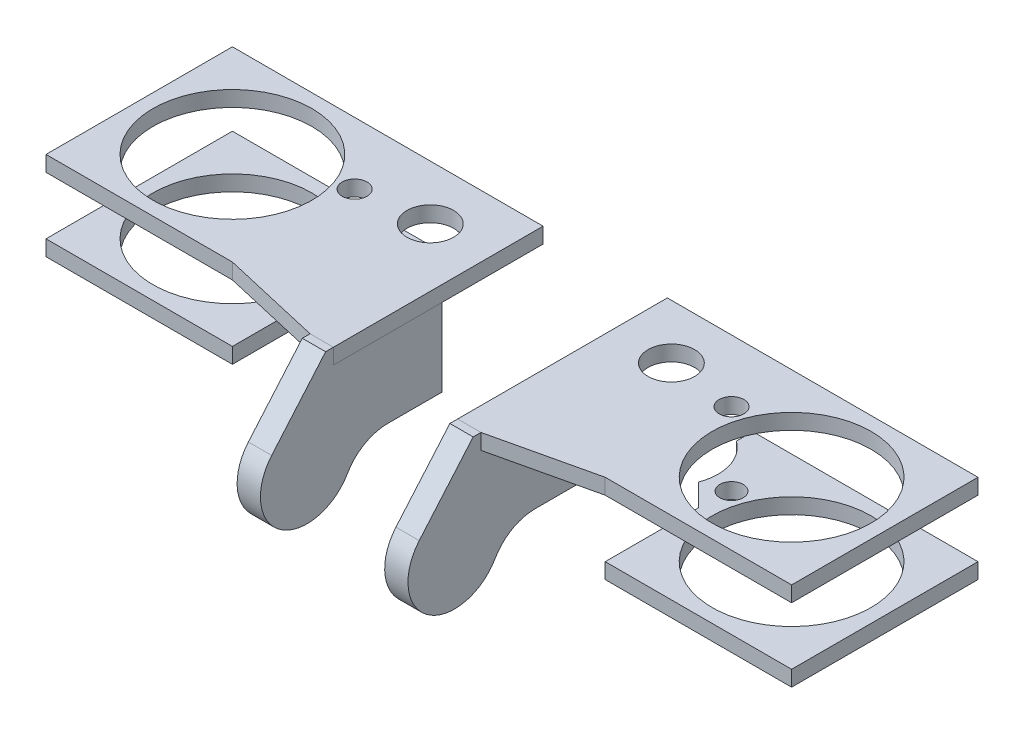
SolidWorks part; units mm, degrees
material "Alum Plate"
ref_plane "Front Plane" through (0, 0, 0) normal (0, 0, 1) x (1, 0, 0)
ref_plane "Top Plane" through (0, 0, 0) normal (0, 1, 0) x (1, 0, 0)
ref_plane "Right Plane" through (0, 0, 0) normal (1, 0, 0) x (0, 0, -1)
sketch "Sketch1" plane through (0, 0, 0) normal (0, 1, 0) x (1, 0, 0)
  line L0 (0, 0) -> (114.3, 0) construction
  line L1 (-114.3, 0) -> (0, 0) construction
  line L3 (-9.525, 158.75) -> (-3.175, 158.75)
  line L4 (-9.525, 158.75) -> (-9.525, 44.45)
  line L5 (-9.525, 44.45) -> (-3.175, 44.45)
  line L6 (-3.175, 158.75) -> (-3.175, 44.45)
  line L7 (-9.525, 158.75) -> (-3.175, 44.45) construction
  line L8 (-9.525, 44.45) -> (-3.175, 158.75) construction
  line L14 (-152.4, -76.2) -> (152.4, -76.2)
  line L18 (-114.3, 0) -> (-49.2756, 15.875) construction
  line L19 (49.2756, 15.875) -> (114.3, 0) construction
  line L20 (-25.4, 38.1) -> (0, 38.1) construction
  line L21 (-6.35, 101.6) -> (0, 101.6)
  line L29 (0, 0) -> (0, -25.4) construction
  line L30 (-114.3, 0) -> (-77.0346, 12.7) construction
  line L43 (-77.0346, 12.7) -> (-49.2756, 15.875) construction
  line L44 (49.2756, 15.875) -> (77.0346, 12.7) construction
  line L55 (77.0346, 12.7) -> (114.3, 0) construction
  line L69 (-152.4, -76.2) -> (-152.4, 38.1)
  line L70 (-152.4, 38.1) -> (152.4, 38.1)
  line L71 (152.4, -76.2) -> (152.4, 38.1)
  line L78 (0, 101.6) -> (0, -25.4)
  line L79 (0, -25.4) -> (0, -152.4) construction
  line L80 (-9.525, -209.55) -> (-3.175, -209.55) construction
  line L81 (-9.525, -209.55) -> (-9.525, -95.25) construction
  line L82 (-9.525, -95.25) -> (-3.175, -95.25) construction
  line L83 (-3.175, -209.55) -> (-3.175, -95.25) construction
  line L84 (-9.525, -209.55) -> (-3.175, -95.25) construction
  line L85 (-9.525, -95.25) -> (-3.175, -209.55) construction
  line L86 (0, -152.4) -> (-6.35, -152.4) construction
  line L87 (-34.925, -76.2) -> (-25.4, -76.2)
  line L88 (-34.925, -76.2) -> (-34.925, 38.1)
  line L89 (-34.925, 38.1) -> (-25.4, 38.1)
  line L90 (-25.4, -76.2) -> (-25.4, 38.1)
  line L91 (34.925, -76.2) -> (25.4, -76.2)
  line L92 (34.925, -76.2) -> (34.925, 38.1)
  line L93 (34.925, 38.1) -> (25.4, 38.1)
  line L94 (25.4, -76.2) -> (25.4, 38.1)
  line L95 (0, 38.1) -> (25.4, 38.1) construction
  circle A0 centre (-114.3, 0) radius 32.5
  circle A1 centre (-114.3, 0) radius 25
  circle A2 centre (114.3, 0) radius 32.5
  circle A3 centre (114.3, 0) radius 25
  circle A4 centre (-49.2756, 15.875) radius 17.5006
  circle A5 centre (49.2756, 15.875) radius 17.5006
  circle A6 centre (-77.0346, 12.7) radius 22.86
  circle A7 centre (77.0346, 12.7) radius 22.86
  point P8 (-6.35, 101.6)
  point P21 (114.3, 32.5)
  point P25 (49.2756, 33.3756)
  point P29 (49.2756, -1.6256)
  point P31 (0, -76.2)
  point P32 (-6.35, -152.4)
  point P62 (146.8, 0)
  dimension "D1" = 50
  dimension "D2" = 65
  dimension "D8" = 35.0012
  dimension "D11" = 127
  dimension "D12" = 63.5
  dimension "D17" = 45.72
  dimension "D3" = 114.3
  dimension "D4" = 6.35
  dimension "D5" = 228.6
  dimension "D6" = 38.1
  dimension "D7" = 38.1
  dimension "D9" = 114.3
  dimension "D10" = 9.525
  dimension "D13" = 9.525
  dimension "D14" = 50.8
  dimension "D15" = 27.94
  dimension "D16" = 39.37
  dimension "D18" = 22.225
  dimension "D19" = 25.4
sketch "Sketch2" plane through (0, 0, 0) normal (1, 0, 0) x (0, 0, -1)
  line L0 (0, 22.225) -> (0, 49.825) construction
  line L1 (-32.5, 53.325) -> (32.5, 53.325)
  line L2 (-32.5, 53.325) -> (-32.5, 46.325)
  line L3 (-32.5, 46.325) -> (32.5, 46.325)
  line L4 (32.5, 53.325) -> (32.5, 46.325)
  line L5 (-32.5, 53.325) -> (32.5, 46.325) construction
  line L6 (-32.5, 46.325) -> (32.5, 53.325) construction
  line L7 (-32.5, 82.55) -> (32.5, 82.55)
  line L8 (-32.5, 82.55) -> (-32.5, 75.55)
  line L9 (-32.5, 75.55) -> (32.5, 75.55)
  line L10 (32.5, 82.55) -> (32.5, 75.55)
  line L11 (-32.5, 82.55) -> (32.5, 75.55) construction
  line L12 (-32.5, 75.55) -> (32.5, 82.55) construction
  line L13 (-25.8191, 0) -> (33.9817, 0) construction
  line L14 (-25.4, 63.5) -> (-152.4, 63.5)
  line L15 (-76.2, 82.55) -> (38.1, 82.55)
  line L16 (-76.2, 82.55) -> (-76.2, 46.325)
  line L17 (-76.2, 46.325) -> (38.1, 46.325)
  line L18 (38.1, 82.55) -> (38.1, 46.325)
  line L19 (-25.4, 25.4) -> (-58.3956, 44.45) construction
  line L20 (-58.3956, 44.45) -> (-25.4, 63.5) construction
  line L21 (101.6, 0) -> (-25.4, 0) construction
  line L22 (-76.2, 76.2) -> (38.1, 76.2)
  line L23 (-76.2, 52.675) -> (38.1, 52.675)
  line L24 (-25.4, 25.4) -> (-25.4, 63.5) construction
  line L25 (-25.4, 7.62) -> (-25.4, 0) construction
  line L26 (32.5, 0) -> (-32.5, 0) construction
  line L40 (-1.6256, 31.6992) -> (33.3756, 31.6992)
  line L41 (-1.6256, 31.6992) -> (-1.6256, 76.2)
  line L42 (-1.6256, 76.2) -> (33.3756, 76.2)
  line L43 (33.3756, 31.6992) -> (33.3756, 76.2)
  line L44 (-1.6256, 31.6992) -> (33.3756, 76.2) construction
  line L45 (-1.6256, 76.2) -> (33.3756, 31.6992) construction
  line L46 (-38.1, 82.55) -> (-38.1, 46.325)
  line L47 (-38.1, 64.4375) -> (0, 64.4375) construction
  line L48 (0, 64.4375) -> (38.1, 64.4375) construction
  circle A0 centre (0, 22.225) radius 22.225
  circle A1 centre (-25.4, 63.5) radius 18.0086
  circle A2 centre (-25.4, 25.4) radius 17.78
  circle A3 centre (-152.4, 63.5) radius 57.15
  circle A4 centre (-25.4, 63.5) radius 4.7625
  circle A5 centre (-58.3956, 44.45) radius 17.78
  point P2 (0, 49.825)
  point P8 (0, 79.05)
  point P16 (-40.6156, 44.45)
  point P28 (-76.1756, 44.45)
  point P32 (15.875, 53.9496)
  point P34 (-209.55, 63.5)
  point P35 (-43.18, 25.4)
  point P36 (-7.62, 25.4)
  point P37 (-7.3914, 63.5)
  point P38 (-43.4086, 63.5)
  dimension "D1" = 44.45
  dimension "D8" = 36.0172
  dimension "D2" = 35.56
  dimension "D11" = 9.525
  dimension "D12" = 35.56
  dimension "D3" = 7
  dimension "D4" = 82.55
  dimension "D5" = 22.225
  dimension "D6" = 6.35
  dimension "D7" = 6.35
  dimension "D9" = 63.5
  dimension "D10" = 44.5008
  dimension "D13" = 38.1
  dimension "D14" = 38.1
  dimension "D15" = 38.1
sketch "Sketch5" plane through (0, 0, 0) normal (0, 1, 0) x (1, 0, 0)
  line L0 (-34.925, -76.2) -> (-34.925, 38.1) construction
  line L1 (-66.421, -7.62) -> (-34.925, -7.62)
  line L2 (-66.421, -7.62) -> (-66.421, -43.18)
  line L3 (-66.421, -43.18) -> (-34.925, -43.18)
  line L4 (-34.925, -7.62) -> (-34.925, -43.18)
  line L5 (-66.421, -7.62) -> (-34.925, -43.18) construction
  line L6 (-66.421, -43.18) -> (-34.925, -7.62) construction
  line L7 (-74.93, -40.6156) -> (-34.925, -40.6156)
  line L8 (-74.93, -40.6156) -> (-74.93, -76.1756)
  line L9 (-74.93, -76.1756) -> (-34.925, -76.1756)
  line L10 (-34.925, -40.6156) -> (-34.925, -76.1756)
  line L11 (-74.93, -40.6156) -> (-34.925, -76.1756) construction
  line L12 (-74.93, -76.1756) -> (-34.925, -40.6156) construction
  line L13 (-66.421, -7.3914) -> (-26.416, -7.3914)
  line L14 (-66.421, -7.3914) -> (-66.421, -43.4086)
  line L15 (-66.421, -43.4086) -> (-26.416, -43.4086)
  line L16 (-26.416, -7.3914) -> (-26.416, -43.4086)
  line L17 (-66.421, -7.3914) -> (-26.416, -43.4086) construction
  line L18 (-66.421, -43.4086) -> (-26.416, -7.3914) construction
  point P0 (-50.673, -25.4)
  point P5 (-54.9275, -58.3956)
  point P10 (-46.4185, -25.4)
  dimension "D2" = 31.496
  dimension "D5" = 40.005
  dimension "D6" = 40.005
ref_plane "Plane1" through (0, 76.2, 0) normal (0, 1, 0) x (1, 0, 0)
ref_plane "Plane2" through (0, 52.675, 0) normal (0, -1, 0) x (-1, 0, 0)
ref_plane "Plane3" through (25.4, 0, 0) normal (1, 0, 0) x (0, 0, -1)
sketch "Sketch6" plane through (25.4, 0, 0) normal (1, 0, 0) x (0, 0, -1)
  line L0 (-25.4, 25.4) -> (-25.4, 63.5) construction
  line L1 (-25.4, 25.4) -> (-58.3956, 44.45) construction
  line L2 (-72.8514, 56.8569) -> (-50.8, 82.55)
  line L3 (-76.2, 82.55) -> (38.1, 82.55) construction
  line L4 (-50.8, 82.55) -> (-47.625, 82.55)
  line L5 (-47.625, 82.55) -> (-47.625, 76.2)
  line L6 (-76.2, 76.2) -> (38.1, 76.2) construction
  line L7 (-47.625, 76.2) -> (-3.175, 76.2)
  line L8 (-3.175, 76.2) -> (-3.175, 44.45)
  line L9 (-3.175, 44.45) -> (-25.4, 44.45)
  arc A1 (-41.8978, 34.925) -> (-25.4, 44.45) centre (-25.4, 25.4) cw
  arc A2 (-41.8978, 34.925) -> (-72.8514, 56.8569) centre (-58.3956, 44.45) cw
  dimension "D1" = 22.225
  dimension "D2" = 22.225
  dimension "D3" = 3.175
extrude "Boss-Extrude1" add sketch "Sketch6" along normal up to vertex (9.525 mm away) up to point (34.925, 0, -38.1)
sketch "Sketch7" plane through (0, 76.2, 0) normal (0, 1, 0) x (1, 0, 0)
  line L0 (25.4, -47.625) -> (34.925, -47.625)
  line L2 (152.4, -76.2) -> (152.4, 38.1) construction
  line L3 (152.4, -38.1) -> (152.4, 38.1)
  line L4 (152.4, 38.1) -> (25.4, 38.1)
  line L5 (25.4, 38.1) -> (25.4, -47.625)
  line L6 (152.4, -38.1) -> (76.2, -38.1)
  line L7 (76.2, -38.1) -> (34.925, -47.625)
  line L8 (114.3, 38.1) -> (114.3, 0) construction
  line L9 (114.3, 0) -> (114.3, -38.1) construction
  circle A0 centre (114.3, 0) radius 32.5 construction
  circle A1 centre (114.3, 0) radius 32.5
  circle A2 centre (77.0346, 12.7) radius 5.08
  circle A3 centre (49.2756, 15.875) radius 9.525
  dimension "D1" = 10.16
  dimension "D2" = 19.05
extrude "Boss-Extrude2" add sketch "Sketch7" along normal up to surface (6.35 mm away) separate body up to face at (30.1625, 82.55, 49.2125)
sketch "Sketch8" plane through (0, 52.675, 0) normal (0, -1, 0) x (-1, 0, 0)
  line L0 (-60.325, 31.3932) -> (-60.325, 38.1)
  line L1 (-76.2, -38.1) -> (-152.4, -38.1)
  line L2 (-76.2, -38.1) -> (-76.2, 38.1) construction
  line L3 (-76.2, 38.1) -> (-152.4, 38.1)
  line L4 (-152.4, -38.1) -> (-152.4, 38.1)
  line L5 (-76.2, -38.1) -> (-152.4, 38.1) construction
  line L6 (-76.2, 38.1) -> (-152.4, -38.1) construction
  line L7 (152.4, 38.1) -> (-152.4, 38.1) construction
  line L8 (-60.325, 38.1) -> (-76.2, 38.1)
  line L9 (-76.2, -38.1) -> (-76.2, 0)
  line L10 (-76.2, 0) -> (-67.0856, 9.1144)
  line L11 (-34.925, -76.2) -> (-34.925, 38.1) construction
  circle A0 centre (-114.3, 0) radius 32.5 construction
  circle A1 centre (-114.3, 0) radius 32.5
  arc A2 (-67.0856, 9.1144) -> (-60.325, 31.3932) centre (-49.2756, 15.875) cw
  circle A3 centre (-77.0346, 12.7) radius 4.7625
  dimension "D1" = 9.525
  dimension "D2" = 19.05
  dimension "D3" = 25.4
  dimension "D4" = 45
  dimension "D5" = 38.1
extrude "Boss-Extrude3" add sketch "Sketch8" along normal up to vertex (6.35 mm away) separate body up to point (0, 46.325, -38.1)
mirror "Mirror2" about plane through (0, 0, 0) normal (1, 0, 0) of bodies 106 108 111
